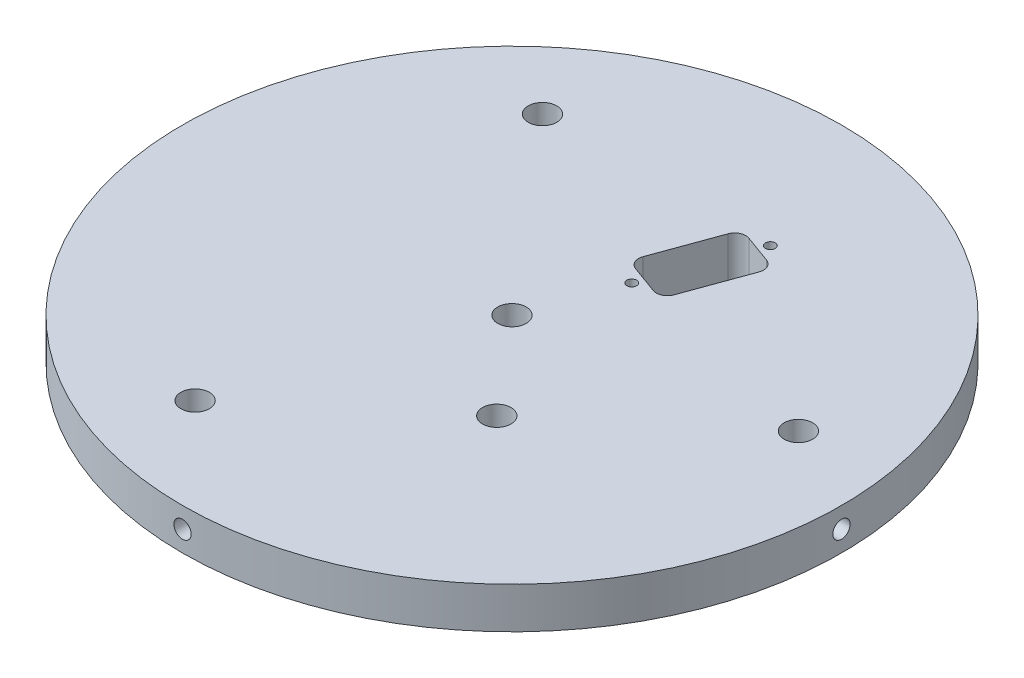
SolidWorks part; units mm, degrees
material "6061-T6 (SS)"
ref_plane "Front Plane" through (0, 0, 0) normal (0, 0, 1) x (1, 0, 0)
ref_plane "Top Plane" through (0, 0, 0) normal (0, 1, 0) x (1, 0, 0)
ref_plane "Right Plane" through (0, 0, 0) normal (1, 0, 0) x (0, 0, -1)
sketch "Sketch1" plane through (0, 0, 0) normal (0, 1, 0) x (1, 0, 0)
  line L0 (0, 0) -> (-50.3682, 60.0265)
  line L1 (0, 0) -> (50.3682, 60.0265)
  line L2 (0, 0) -> (0, 72.1431) construction
  circle A0 centre (0, 0) radius 78.359
  circle A1 centre (0, 0) radius 76.1746
  circle A2 centre (0, 0) radius 76.1746
  dimension "D1" = 156.718
  dimension "D2" = 152.3492
  dimension "D3" = 152.3492
  dimension "D4" = 80
extrude "Boss-Extrude1" add sketch "Sketch1" along normal blind 25.4 contours L2 A2 L1 A0 | L2 A1 L1 A2 | L2 A2 L1 A1 | L2 A0 L1 A2 | A2 L2 A1 L0 | A0 L2 A2 L0 | A2 L2 A0 L0 | A1 L2 A2 L0 region at (0, 0, 13.3592) region at (-23.5316, 0, -29.974) region at (-33.0764, 0, 70.9325) region at (-48.8794, 0, -59.85)
ref_plane "Plane1" through (0, 12.7, 0) normal (0, 1, 0) x (1, 0, 0)
sketch "Sketch6" plane through (0, 25.4, 0) normal (0, 1, 0) x (1, 0, 0)
  circle A0 centre (0, 0) radius 76.1746
  dimension "D1" = 152.3492
extrude "Boss-Extrude5" add sketch "Sketch6" along normal blind 9.525
sketch "Sketch7" plane through (0, 0, 0) normal (0, -1, 0) x (1, 0, 0)
  circle A0 centre (0, 0) radius 76.1746
  dimension "D1" = 152.3492
extrude "Boss-Extrude6" add sketch "Sketch7" along normal blind 9.525
sketch "Sketch8" plane through (0, -9.525, 0) normal (0, -1, 0) x (1, 0, 0)
  circle A0 centre (0, 0) radius 73.025
  dimension "D1" = 146.05
extrude "Cut-Extrude5" cut sketch "Sketch8" against normal up to surface (34.925 mm away) up to face at (0, 25.4, 76.1746)
ref_plane "Plane2" through (0, 0, -76.1746) normal (0, 0, -1) x (-1, 0, 0)
ref_plane "Plane5" through (0, 25.4, 0) normal (0, 1, 0) x (1, 0, 0)
ref_axis "Axis1" through (0, 0, 0) along (0, 1, 0)
sketch "Sketch3" plane through (0, 0, -76.1746) normal (0, 0, -1) x (-1, 0, 0)
  line L4 (76.1746, 0) -> (-76.1746, 0)
  line L5 (-76.1746, -9.525) -> (76.1746, -9.525)
  line L6 (76.1746, 25.4) -> (-76.1746, 25.4)
  line L7 (76.1746, 34.925) -> (-76.1746, 34.925)
  line L8 (0, 34.925) -> (0, 25.4) construction
  line L9 (0, 0) -> (0, -9.525) construction
  circle A0 centre (0, 30.1625) radius 2
  circle A1 centre (0, -4.7625) radius 2
  point P12 (0, 30.1625)
  point P13 (0, -4.7625)
  point P14 (-77.5445, 179.1871)
  dimension "D1" = 4
extrude "Cut-Extrude2" cut sketch "Sketch3" against normal blind 9.525 contours L8 A0 | L8 A0 | L9 A1 | L9 A1 region at (0, 30.1625, -76.1746) region at (0, -4.7625, -76.1746)
extrude "Cut-Extrude3" cut sketch "Sketch1<7>" against normal blind 9.525 from surface contours L2 A1 L1 A2 | A1 L2 A2 L0 | A2 L2 A0 L0 | L2 A2 L1 A0 region at (-23.5316, 0, -29.974) region at (-48.8794, 0, -59.85) starting at plane "Plane5"
sketch "Sketch1<7>" plane through (0, 0, 0) normal (0, 1, 0) x (1, 0, 0) same geometry as "Sketch1"
pattern_circular "CirPattern2" count 3 over 360 about axis through (0, 0, 0) along (0, 1, 0) of "Cut-Extrude3"
ref_plane "Plane3" through (0, 34.925, 0) normal (0, 1, 0) x (1, 0, 0)
sketch "Sketch4" plane through (0, 34.925, 0) normal (0, 1, 0) x (1, 0, 0)
  circle A0 centre (0, 0) radius 73.025
  dimension "D1" = 146.05
extrude "Boss-Extrude4" add sketch "Sketch4" against normal blind 9.525
pattern_circular "CirPattern3" count 4 over 360 about axis through (0, 0, 0) along (0, 1, 0) of "Cut-Extrude2"
sketch "Sketch9" plane through (0, 34.925, 0) normal (0, 1, 0) x (1, 0, 0)
  line L0 (0, 0) -> (-26.8004, -73.6334) construction
  line L1 (0, 0) -> (32.0596, -38.2071) construction
  circle A0 centre (0, 0) radius 3.3
  circle A1 centre (-19.5465, -53.7034) radius 3.3
  circle A2 centre (-36.7353, 43.7794) radius 3.3
  circle A3 centre (56.2818, 9.924) radius 3.3
  circle A4 centre (18.3677, -21.8897) radius 3.3
  point P15 (0, 0)
  dimension "D1" = 6.6
  dimension "D2" = 6.6
  dimension "D6" = 6.6
  dimension "D3" = 57.15
  dimension "D4" = 60
  dimension "D7" = 28.575
extrude "Cut-Extrude6" cut sketch "Sketch9" against normal through all
sketch "Sketch10" plane through (0, 25.4, 0) normal (0, 1, 0) x (1, 0, 0)
  circle A0 centre (0, 0) radius 82.3228
extrude "Cut-Extrude7" cut sketch "Sketch10" against normal through all
hole_wizard "Tap Drill for #4-40 Tap1" positions "Sketch12" profile "Sketch13" hole size "#4-40" standard "ANSI Inch" end condition through all
sketch "Sketch12" plane through (0, 34.925, 0) normal (0, 1, 0) x (1, 0, 0)
  line L0 (0, 0) -> (18.6243, 51.1699) construction
  line L2 (0, 0) -> (-36.7353, 43.7794) construction
  circle A0 centre (0, 0) radius 21.59 construction
  point P0 (7.3842, 20.288)
  point P2 (15.9347, 43.7803)
  dimension "D3" = 43.18
  dimension "D1" = 60
  dimension "D2" = 25
sketch "Sketch13" plane through (7.3842, 34.925, -20.288) normal (1, 0, 0) x (0, 0, 1)
  line L0 (0, 0) -> (0, 9.525)
  line L1 (0, 9.525) -> (1.1303, 9.525)
  line L2 (1.1303, 9.525) -> (1.1303, 0)
  line L5 (1.1303, 0) -> (0, 0)
  line L11 (0, -6.35) -> (0, 107.95) construction
  dimension "Thru Hole Dia." = 2.2606
  dimension "Thru Hole Depth" = 9.525
sketch "Sketch14" plane through (0, 34.925, 0) normal (0, 1, 0) x (1, 0, 0)
  line L0 (7.3842, 20.288) -> (15.9347, 43.7803) construction
  line L1 (14.6438, 22.7814) -> (19.8932, 37.2038)
  line L2 (11.3883, 21.2633) -> (4.9439, 23.6089)
  line L3 (18.3751, 40.4594) -> (11.9307, 42.8049)
  line L4 (3.4258, 26.8644) -> (8.6751, 41.2868)
  arc A0 (19.8932, 37.2038) -> (18.3751, 40.4594) centre (17.5063, 38.0725) ccw
  arc A1 (11.9307, 42.8049) -> (8.6751, 41.2868) centre (11.0619, 40.4181) ccw
  arc A2 (11.3883, 21.2633) -> (14.6438, 22.7814) centre (12.257, 23.6501) ccw
  arc A3 (4.9439, 23.6089) -> (3.4258, 26.8644) centre (5.8126, 25.9957) cw
  point P0 (8.1661, 22.4361)
  dimension "D4" = 2.54
  dimension "D5" = 2.54
  dimension "D1" = 2.286
  dimension "D2" = 2.286
  dimension "D3" = 11.938
extrude "Cut-Extrude9" cut sketch "Sketch14" against normal through all
equation "\"AB_Coupler_OD_Length\"= 1in"
equation "\"AB_Coupling_Section_Length\"= 0.375in"
equation "\"AB_Coupler_Length\"= \"AB_Coupler_OD_Length\" + \"AB_Coupling_Section_Length\" * 2"
equation "\"Cutout_Angle\" = 80"
equation "\"AB_Coupler_Num_Screws\"= 6"
equation "\"Num_Cutouts\" = 3"
equation "\"AB_Coupler_OD\"= 6.17in"
equation "\"AB_Coupler_ID\"= 5.75in"
equation "\"AB_Coupler_Surface_Diameter\"= 5.998in"
equation "\"D2@Sketch1\"=\"Bodytube_ID\""
equation "\"AB_Coupling_Screw_Diameter\"= 0.1065in"
equation "\"Aft_Section_Length\"= 39in"
equation "\"Aft_Lower_Length\"= 22in"
equation "\"Aft_Upper_Length\"= \"Aft_Section_Length\" - \"Aft_Lower_Length\" - \"AB_Coupler_OD_Length\""
equation "\"Mid_Coupler_Length\" = 13in"
equation "\"Lead_Screw_Dist\" = 2.25in"
equation "\"Lead_Screw_Diam\" = 11mm"
equation "\"Lead_Screw_Length\" = (\"Mid_Coupler_Length\" + 2*0.375in + 2*0.5in)"
equation "\"Bodytube_OD\" = 6.17in"
equation "\"Paddle_Pin_Offset\" = .25in"
equation "\"Bodytube_ID\" = 5.998in"
equation "\"Paddle_Pin_Radius\" = 2.25in"
equation "\"D1@Sketch4\"=\"AB_Coupler_ID\""
equation "\"D1@Sketch6\"=\"AB_Coupler_Surface_Diameter\""
equation "\"D1@Boss-Extrude5\"=\"AB_Coupling_Section_Length\""
equation "\"D1@Sketch7\"=\"AB_Coupler_Surface_Diameter\""
equation "\"D1@Boss-Extrude6\"=\"AB_Coupling_Section_Length\""
equation "\"D1@Sketch8\"=\"AB_Coupler_ID\""
equation "\"D3@Sketch9\"=\"Paddle_Pin_Radius\""
equation "\"Motor_OD\" = 4in"
equation "\"Fwd_Tube_Length\" = 40in"
equation "\"Mid_Tube_Length\" = 1in"
equation "\"AB_Paddle_Height\" = 0.375in"
equation "\"AB_Central_Bushing_Length\" = .75in"
equation "\"Paddle_Gear_OD\" = 3.2in"
equation "\"Fwd_BKHD_From_Top\" = 18in"
equation "\"Fin_Thickness\"= .118in"
equation "\"Guiderail_Cutout_Diameter\"= 1.5in"
equation "\"DB9_Hole_Dist\" = 25mm"
equation "\"D2@Sketch12\"=\"DB9_Hole_Dist\""
equation "\"Drive_Gear_OD\" = 1.7in"
equation "\"D3@Sketch12\"=\"Drive_Gear_OD\""
equation "\"DB9_Relief_Width\" = 0.47in"
equation "\"D3@Sketch14\"=\"DB9_Relief_Width\""
equation "\"DB9_Relief_Hole_Offset\" = 0.09in"
equation "\"D2@Sketch14\"=\"DB9_Relief_Hole_Offset\""
equation "\"D1@Sketch14\"=\"DB9_Relief_Hole_Offset\""
equation "\"SS_Paddle_Pin_Radius\" = 2.25*0.66in"
equation "\"Airbrakes_Wire_Hole_Dia\" = .25in"
equation "\"Airbrakes_Wire_Hole_Dist\" = 1.1in"
equation "\"Servo_Gear_Offset\" = 0.5in"
